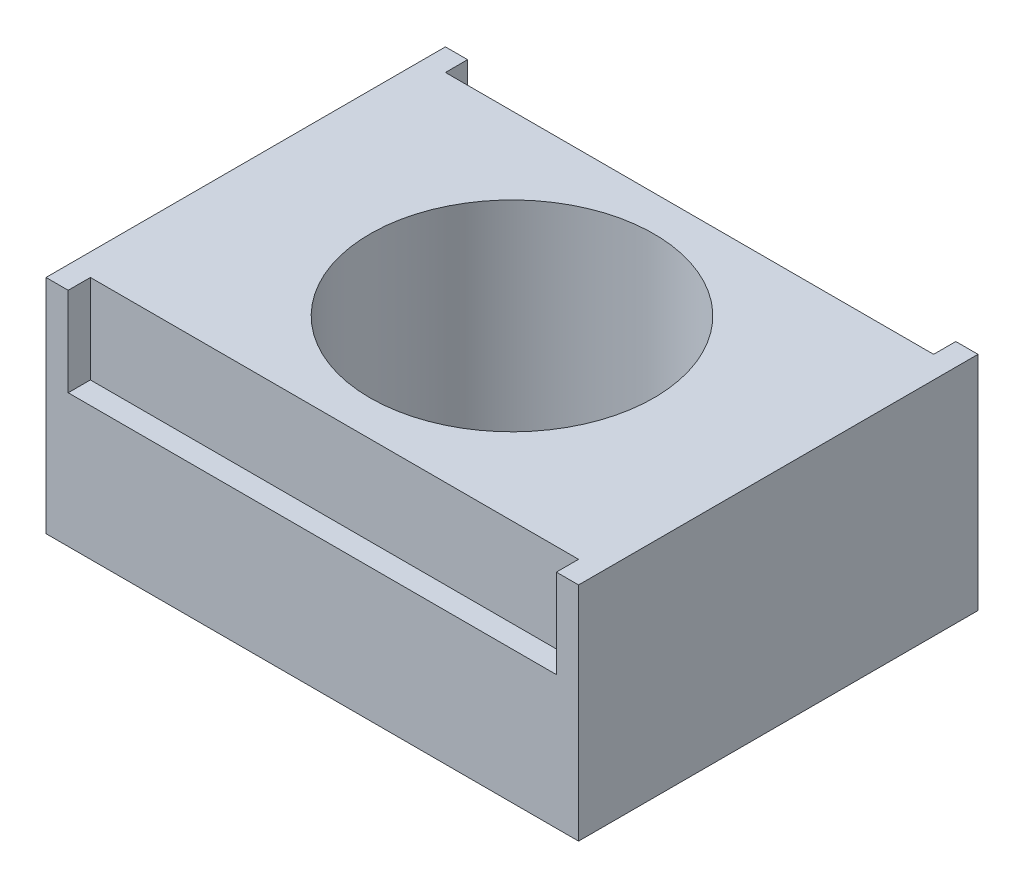
SolidWorks part; units mm, degrees
material "ABS"
ref_plane "Front Plane" through (0, 0, 0) normal (0, 0, 1) x (1, 0, 0)
ref_plane "Top Plane" through (0, 0, 0) normal (0, 1, 0) x (1, 0, 0)
ref_plane "Right Plane" through (0, 0, 0) normal (1, 0, 0) x (0, 0, -1)
sketch "Sketch1" plane through (0, 0, 0) normal (0, 1, 0) x (1, 0, 0)
  line L1 (12, -9) -> (-12, -9)
  line L2 (12, -9) -> (12, 9)
  line L3 (12, 9) -> (-12, 9)
  line L4 (-12, -9) -> (-12, 9)
  line L5 (12, -9) -> (-12, 9) construction
  line L6 (12, 9) -> (-12, -9) construction
  circle A0 centre (0, 0) radius 6.4
  point P0 (0, 0)
  dimension "D3" = 12.8
  dimension "D1" = 18
  dimension "D2" = 24
extrude "Boss-Extrude1" add sketch "Sketch1" along normal blind 10
sketch "Sketch2" plane through (0, 10, 0) normal (0, 1, 0) x (1, 0, 0)
  line L0 (12, 9) -> (-12, 9) construction
  line L1 (-11, 9) -> (11, 9)
  line L2 (-11, 9) -> (-11, 8)
  line L3 (-11, 8) -> (11, 8)
  line L4 (11, 9) -> (11, 8)
  line L5 (-14.8036, 0) -> (15.4358, 0) construction
  line L6 (0, 13.0337) -> (0, -13.1458) construction
  line L7 (-11, -9) -> (11, -9)
  line L8 (11, -9) -> (11, -8)
  line L9 (-11, -8) -> (11, -8)
  line L10 (-11, -9) -> (-11, -8)
  dimension "D1" = 22
  dimension "D2" = 1
extrude "Cut-Extrude1" cut sketch "Sketch2" against normal blind 4
shell "Shell1" thickness 1.1 removed face at (0, 0, 0)
